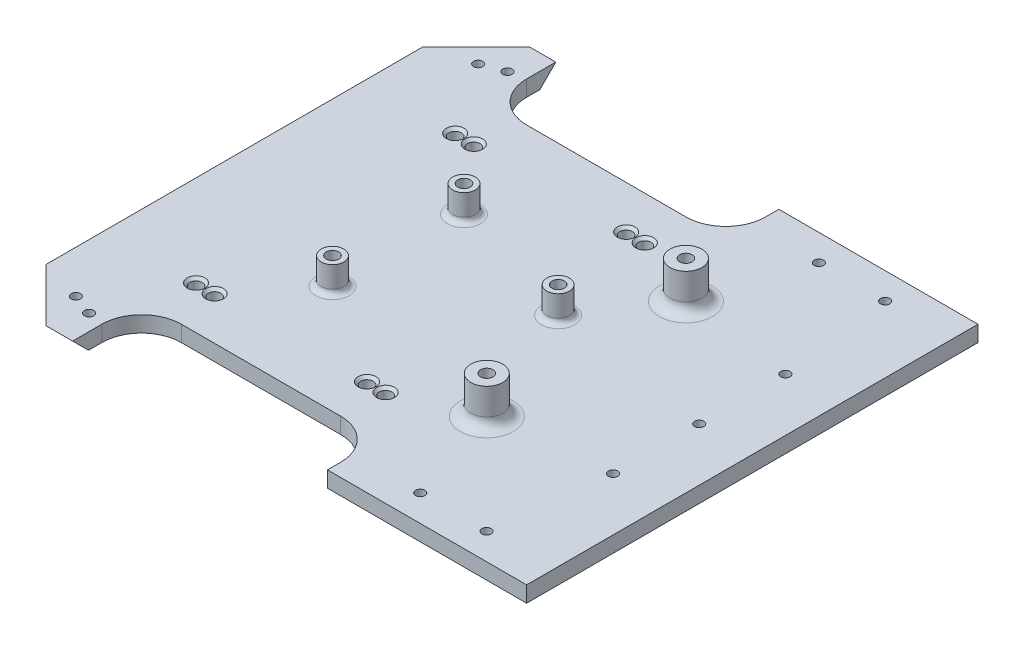
SolidWorks part; units mm, degrees
material "ABS"
ref_plane "Front Plane" through (0, 0, 0) normal (0, 0, 1) x (1, 0, 0)
ref_plane "Top Plane" through (0, 0, 0) normal (0, 1, 0) x (1, 0, 0)
ref_plane "Right Plane" through (0, 0, 0) normal (1, 0, 0) x (0, 0, -1)
sketch "Sketch1" plane through (0, 0, 0) normal (0, 1, 0) x (1, 0, 0)
  line L1 (-97.5, 85) -> (97.5, 85)
  line L2 (-97.5, 85) -> (-97.5, -85)
  line L3 (-97.5, -85) -> (97.5, -85)
  line L4 (97.5, 85) -> (97.5, -85)
  line L5 (-97.5, 85) -> (97.5, -85) construction
  line L6 (-97.5, -85) -> (97.5, 85) construction
  point P0 (0, 0)
  dimension "D1" = 195
  dimension "D2" = 170
extrude "Boss-Extrude1" add sketch "Sketch1" along normal blind 6
sketch "Sketch2" plane through (0, 6, 0) normal (0, 1, 0) x (1, 0, 0)
  line L0 (-97.5, -85) -> (-67.5, -85) construction
  line L1 (-97.5, -85) -> (97.5, -85) construction
  line L2 (0, 0) -> (-97.5, 0) construction
  line L3 (-67.5, -85) -> (22.5, -85)
  line L4 (-67.5, -85) -> (-67.5, -65)
  line L5 (-67.5, -65) -> (22.5, -65)
  line L6 (22.5, -85) -> (22.5, -65)
  line L7 (-97.5, 85) -> (-97.5, -85) construction
  line L8 (-67.5, 65) -> (22.5, 65)
  line L9 (22.5, 85) -> (22.5, 65)
  line L10 (-67.5, 85) -> (22.5, 85)
  line L11 (-67.5, 85) -> (-67.5, 65)
  dimension "D1" = 30
  dimension "D2" = 90
  dimension "D3" = 20
extrude "Cut-Extrude1" cut sketch "Sketch2" against normal through all
fillet "Fillet1" radius 15 4 edges at (22.5, 3, -65) (-67.5, 3, -65) (-67.5, 3, 65) (22.5, 3, 65)
sketch "Sketch3" plane through (0, 6, 0) normal (0, 1, 0) x (1, 0, 0)
  line L0 (0, 0) -> (-97.5, 0) construction
  line L1 (-67.5, 85) -> (-97.5, 85)
  line L2 (-67.5, 85) -> (-67.5, 91)
  line L3 (-67.5, 91) -> (-97.5, 91)
  line L4 (-97.5, 85) -> (-97.5, 91)
  line L5 (-97.5, 85) -> (-97.5, -85) construction
  line L6 (-67.5, -91) -> (-97.5, -91)
  line L7 (-97.5, -85) -> (-97.5, -91)
  line L8 (-67.5, -85) -> (-97.5, -85)
  line L9 (-67.5, -85) -> (-67.5, -91)
  dimension "D1" = 6
extrude "Boss-Extrude2" add sketch "Sketch3" against normal up to surface (6 mm away) up to face at (-16.875, 0, 0)
chamfer "Chamfer1" distance 20 angle 45 2 edges at (-97.5, 3, 91) (-97.5, 3, -91)
sketch "Sketch4" plane through (0, 6, 0) normal (0, 1, 0) x (1, 0, 0)
  line L0 (-67.5, 91) -> (-67.5, 80) construction
  line L1 (-67.5, 91.1) -> (-88.5, 91.1) construction
  line L2 (-67.5, 91.1) -> (-67.5, 68.1) construction
  line L3 (-67.5, 68.1) -> (-88.5, 68.1) construction
  line L4 (-88.5, 91.1) -> (-88.5, 68.1) construction
  line L5 (-81.5, 75.7667) -> (-73.5, 75.7667) construction
  line L6 (-73.5, 75.7667) -> (-73.5, 78.7667) construction
  line L7 (-88.5, 68.1) -> (-81.5, 75.7667) construction
  line L8 (-81.5, 75.7667) -> (-74.5, 83.4333) construction
  line L9 (-74.5, 83.4333) -> (-67.5, 91.1) construction
  line L10 (-97.5, 0) -> (0, 0) construction
  line L11 (-97.5, 71) -> (-97.5, -71) construction
  line L12 (-67.5, 91) -> (-77.5, 91) construction
  circle A0 centre (-81.5, 75.7667) radius 1.75
  circle A1 centre (-74.5, 83.4333) radius 1.75 construction
  circle A2 centre (-74.5, -83.4333) radius 1.75 construction
  circle A3 centre (-81.5, -75.7667) radius 1.75
  circle A6 centre (-73.5, 78.7667) radius 1.75
  circle A7 centre (-73.5, -78.7667) radius 1.75
  dimension "D4" = 3.5
  dimension "D5" = 3.5
  dimension "D6" = 3
  dimension "D8" = 3.5
  dimension "D1" = 23
  dimension "D2" = 21
  dimension "D3" = 0.1
  dimension "D7" = 8
extrude "Cut-Extrude2" cut sketch "Sketch4" against normal through all
sketch "Sketch7" plane through (0, 0, 0) normal (0, -1, 0) x (1, 0, 0)
  line L0 (97.5, 85) -> (97.5, -85) construction
  line L1 (22.5, 85.1) -> (97.5, 85.1) construction
  line L2 (22.5, 85.1) -> (22.5, 65) construction
  line L3 (22.5, 65) -> (97.5, 65) construction
  line L4 (97.5, 85.1) -> (97.5, 65) construction
  line L5 (22.5, 85) -> (22.5, 80) construction
  line L6 (22.5, 85) -> (97.5, 85) construction
  line L7 (22.5, 75.05) -> (47.5, 75.05) construction
  line L8 (47.5, 75.05) -> (72.5, 75.05) construction
  line L9 (72.5, 75.05) -> (97.5, 75.05) construction
  line L10 (0, 0) -> (97.5, 0) construction
  circle A0 centre (47.5, 75.05) radius 1.75
  circle A1 centre (72.5, 75.05) radius 1.75
  circle A2 centre (72.5, -75.05) radius 1.75
  circle A3 centre (47.5, -75.05) radius 1.75
  dimension "D3" = 3.5
  dimension "D4" = 3.5
  dimension "D1" = 0.1
  dimension "D2" = 20.1
extrude "Cut-Extrude5" cut sketch "Sketch7" against normal through all
sketch "Sketch8" plane through (0, 0, 0) normal (0, -1, 0) x (1, 0, 0)
  line L0 (97.5, 0) -> (57.5, 0) construction
  line L1 (97.5, 85) -> (97.5, -85) construction
  line L2 (77.5, 64.9) -> (77.5, 32.45) construction
  line L3 (57.5, 64.9) -> (97.5, 64.9) construction
  line L4 (57.5, 64.9) -> (57.5, -64.9) construction
  line L5 (57.5, -64.9) -> (97.5, -64.9) construction
  line L6 (97.5, 64.9) -> (97.5, -64.9) construction
  line L7 (57.5, 64.9) -> (97.5, -64.9) construction
  line L8 (57.5, -64.9) -> (97.5, 64.9) construction
  line L9 (77.5, 32.45) -> (77.5, 0) construction
  line L10 (77.5, 0) -> (77.5, -32.45) construction
  line L11 (77.5, -32.45) -> (77.5, -64.9) construction
  circle A0 centre (77.5, 32.45) radius 1.75
  circle A1 centre (77.5, 0) radius 1.75
  circle A2 centre (77.5, -32.45) radius 1.75
  point P5 (77.5, 0)
  dimension "D3" = 3.5
  dimension "D4" = 3.5
  dimension "D5" = 3.5
  dimension "D1" = 40
  dimension "D2" = 129.8
extrude "Cut-Extrude6" cut sketch "Sketch8" against normal through all
sketch "Sketch6" plane through (0, 0, 0) normal (0, -1, 0) x (1, 0, 0)
  line L0 (0, 0) -> (-97.5, 0) construction
  line L1 (-97.5, -71) -> (-97.5, 71) construction
  circle A1 centre (-81.5, 75.7667) radius 3.5
  circle A3 centre (-81.5, -75.7667) radius 3.5
  circle A4 centre (47.5, 75.05) radius 3.5
  circle A5 centre (72.5, 75.05) radius 3.5
  circle A6 centre (47.5, -75.05) radius 3.5
  circle A7 centre (72.5, -75.05) radius 3.5
  circle A8 centre (77.5, 32.45) radius 3.5
  circle A9 centre (77.5, 0) radius 3.5
  circle A10 centre (77.5, -32.45) radius 3.5
  circle A11 centre (-73.5, 78.7667) radius 3.5
  circle A12 centre (-73.5, -78.7667) radius 3.5
  dimension "D1" = 7
  dimension "D2" = 7
  dimension "D3" = 7
  dimension "D4" = 7
  dimension "D5" = 7
  dimension "D6" = 7
  dimension "D7" = 7
extrude "Cut-Extrude4" cut sketch "Sketch6" against normal blind 3
chamfer "Chamfer3" distance 6 angle 45 2 edges at (-72.5, 0, -91) (-72.5, 0, 91)
sketch "Sketch9" plane through (0, 6, 0) normal (0, 1, 0) x (1, 0, 0)
  line L0 (8.2, 85) -> (8.2, 48.8) construction
  line L1 (97.5, 85) -> (22.5, 85) construction
  line L2 (8.2, 48.8) -> (8.2, -48.8) construction
  line L3 (8.2, -48.8) -> (8.2, -85) construction
  line L4 (22.5, -85) -> (97.5, -85) construction
  line L5 (8.2, 48.8) -> (-63.2, 48.8) construction
  line L6 (-63.2, 48.8) -> (-63.2, -48.8) construction
  line L7 (-63.2, -48.8) -> (8.2, -48.8) construction
  line L8 (97.5, -85) -> (97.5, 85) construction
  circle A0 centre (8.2, 48.8) radius 2.35
  circle A1 centre (8.2, -48.8) radius 2.35
  circle A2 centre (-63.2, 48.8) radius 2.35
  circle A3 centre (-63.2, -48.8) radius 2.35
  circle A4 centre (-56.2, 48.8) radius 2.35
  circle A5 centre (1.2, 48.8) radius 2.35
  circle A6 centre (1.2, -48.8) radius 2.35
  circle A7 centre (-56.2, -48.8) radius 2.35
  dimension "D2" = 4.7
  dimension "D3" = 4.7
  dimension "D5" = 4.7
  dimension "D6" = 4.7
  dimension "D12" = 4.7
  dimension "D13" = 4.7
  dimension "D14" = 4.7
  dimension "D15" = 4.7
  dimension "D1" = 97.6
  dimension "D4" = 71.4
  dimension "D7" = 89.3
  dimension "D8" = 7
  dimension "D9" = 7
  dimension "D10" = 7
  dimension "D11" = 7
extrude "Cut-Extrude7" cut sketch "Sketch9" against normal blind 4.5
chamfer "Chamfer4" distance 1 angle 45 8 edges at (8.2, 6, -46.45) (1.2, 6, -46.45) (-56.2, 6, -46.45) (-63.2, 6, -46.45) (8.2, 6, 51.15) (1.2, 6, 51.15) (-56.2, 6, 51.15) (-63.2, 6, 51.15)
sketch "Sketch10" plane through (0, 6, 0) normal (0, 1, 0) x (1, 0, 0)
  line L0 (35, 37.5) -> (35, -37.5) construction
  line L1 (97.5, -85) -> (97.5, 85) construction
  line L2 (35, 37.5) -> (35, 85) construction
  line L3 (97.5, 85) -> (22.5, 85) construction
  line L4 (35, -37.5) -> (35, -85) construction
  line L5 (22.5, -85) -> (97.5, -85) construction
  circle A0 centre (35, 37.5) radius 6
  circle A1 centre (35, -37.5) radius 6
  dimension "D3" = 12
  dimension "D4" = 12
  dimension "D1" = 62.5
  dimension "D2" = 75
extrude "Boss-Extrude3" add sketch "Sketch10" along normal blind 14
sketch "Sketch11" plane through (0, 20, 0) normal (0, 1, 0) x (1, 0, 0)
  circle A0 centre (35, 37.5) radius 2.35
  circle A1 centre (35, -37.5) radius 2.35
  dimension "D1" = 4.7
  dimension "D2" = 4.7
extrude "Cut-Extrude8" cut sketch "Sketch11" against normal blind 9
fillet "Fillet2" radius 4 2 edges at (35, 6, -31.5) (35, 6, 43.5)
sketch "Sketch12" [suppressed] plane through (0, 6, 0) normal (0, 1, 0) x (1, 0, 0)
  line L0 (-9.5985, -30.04) -> (-9.5985, -65) construction
  line L1 (-27.5, 30.04) -> (17.5, 30.04) construction
  line L2 (-27.5, 30.04) -> (-27.5, -30.04) construction
  line L3 (-27.5, -30.04) -> (17.5, -30.04) construction
  line L4 (17.5, 30.04) -> (17.5, -30.04) construction
  line L5 (7.5, -65) -> (-52.5, -65) construction
  line L6 (-9.5985, 30.04) -> (-9.5985, 65) construction
  line L7 (-52.5, 65) -> (7.5, 65) construction
  line L8 (97.5, -85) -> (97.5, 85) construction
  circle A0 centre (-27.5, 30.04) radius 4.25
  circle A1 centre (17.5, 30.04) radius 4.25
  circle A2 centre (17.5, -30.04) radius 4.25
  circle A3 centre (-27.5, -30.04) radius 4.25
  dimension "D3" = 8.5
  dimension "D4" = 8.5
  dimension "D5" = 8.5
  dimension "D6" = 8.5
  dimension "D1" = 60.08
  dimension "D2" = 45
  dimension "D7" = 80
extrude "Boss-Extrude4" [suppressed] add sketch "Sketch12" along normal blind 7
sketch "Sketch13" [suppressed] plane through (0, 13, 0) normal (0, 1, 0) x (1, 0, 0)
  circle A0 centre (-27.5, 30.04) radius 2.35
  circle A1 centre (17.5, 30.04) radius 2.35
  circle A2 centre (-27.5, -30.04) radius 2.35
  circle A3 centre (17.5, -30.04) radius 2.35
  dimension "D1" = 4.7
  dimension "D2" = 4.7
  dimension "D3" = 4.7
  dimension "D4" = 4.7
extrude "Cut-Extrude9" [suppressed] cut sketch "Sketch13" against normal blind 10
fillet "Fillet3" [suppressed] radius 2
chamfer "Chamfer5" [suppressed] distance 1 angle 45
sketch "Sketch14" [suppressed] plane through (0, 6, 0) normal (0, 1, 0) x (1, 0, 0)
  line L0 (-97.5, 71) -> (-97.5, -71) construction
  line L1 (-84.5, 30) -> (-80.5, 30)
  line L2 (-84.5, 30) -> (-84.5, -30)
  line L3 (-84.5, -30) -> (-80.5, -30)
  line L4 (-80.5, 30) -> (-80.5, -30)
  line L5 (-39.5, 30) -> (-35.5, 30)
  line L6 (-39.5, 30) -> (-39.5, -30)
  line L7 (-39.5, -30) -> (-35.5, -30)
  line L8 (-35.5, 30) -> (-35.5, -30)
  line L9 (-37.5, -30) -> (-37.5, -65) construction
  line L10 (7.5, -65) -> (-52.5, -65) construction
  line L11 (-37.5, 30) -> (-37.5, 65) construction
  line L12 (-52.5, 65) -> (7.5, 65) construction
  dimension "D1" = 4
  dimension "D2" = 4
  dimension "D3" = 41
  dimension "D4" = 13
  dimension "D5" = 60
extrude "Boss-Extrude5" [suppressed] add sketch "Sketch14" along normal blind 8
sketch "Sketch15" [suppressed] plane through (-84.5, 0, 0) normal (-1, 0, 0) x (0, 0, 1)
  line L0 (-30, 6) -> (30, 6) construction
  line L1 (-15, 6) -> (15, 6)
  line L2 (-15, 6) -> (-15, 10)
  line L3 (-15, 10) -> (15, 10)
  line L4 (15, 6) -> (15, 10)
  line L5 (-15, 8) -> (-30, 8) construction
  line L6 (-30, 14) -> (-30, 6) construction
  line L7 (15, 8) -> (30, 8) construction
  line L8 (30, 14) -> (30, 6) construction
  dimension "D1" = 30
  dimension "D2" = 4
extrude "Cut-Extrude10" [suppressed] cut sketch "Sketch15" against normal up to surface (49 mm away)
fillet "Fillet4" [suppressed] radius 2
fillet "Fillet6" [suppressed] radius 2
sketch "Sketch16" plane through (0, 6, 0) normal (0, 1, 0) x (1, 0, 0)
  line L0 (97.5, -85) -> (97.5, 85) construction
  line L2 (15.5, 8.878) -> (15.5, 34.988) construction
  line L3 (15.5, 8.878) -> (15.5, -34.988) construction
  line L4 (15.5, 34.988) -> (15.5, 65) construction
  line L5 (-52.5, 65) -> (7.5, 65) construction
  line L6 (15.5, -34.988) -> (15.5, -65) construction
  line L7 (7.5, -65) -> (-52.5, -65) construction
  circle A0 centre (15.5, 8.878) radius 4.25
  circle A1 centre (-35.2, 24.118) radius 4.25
  circle A2 centre (-36.47, -24.142) radius 4.25
  dimension "D8" = 8.5
  dimension "D9" = 8.5
  dimension "D10" = 8.5
  dimension "D1" = 51.97
  dimension "D2" = 50.7
  dimension "D3" = 15.24
  dimension "D4" = 33.02
  dimension "D5" = 82
  dimension "D6" = 26.11
  dimension "D7" = 43.866
extrude "Boss-Extrude6" add sketch "Sketch16" along normal blind 10
fillet "Fillet7" radius 2 3 edges at (-35.2, 6, -19.868) (15.5, 6, -4.628) (-36.47, 6, 28.392)
sketch "Sketch17" plane through (0, 16, 0) normal (0, 1, 0) x (1, 0, 0)
  circle A0 centre (-35.2, 24.118) radius 2.35
  circle A1 centre (15.5, 8.878) radius 2.35
  circle A2 centre (-36.47, -24.142) radius 2.35
  dimension "D1" = 4.7
  dimension "D2" = 4.7
  dimension "D3" = 4.7
extrude "Cut-Extrude11" cut sketch "Sketch17" against normal blind 8
